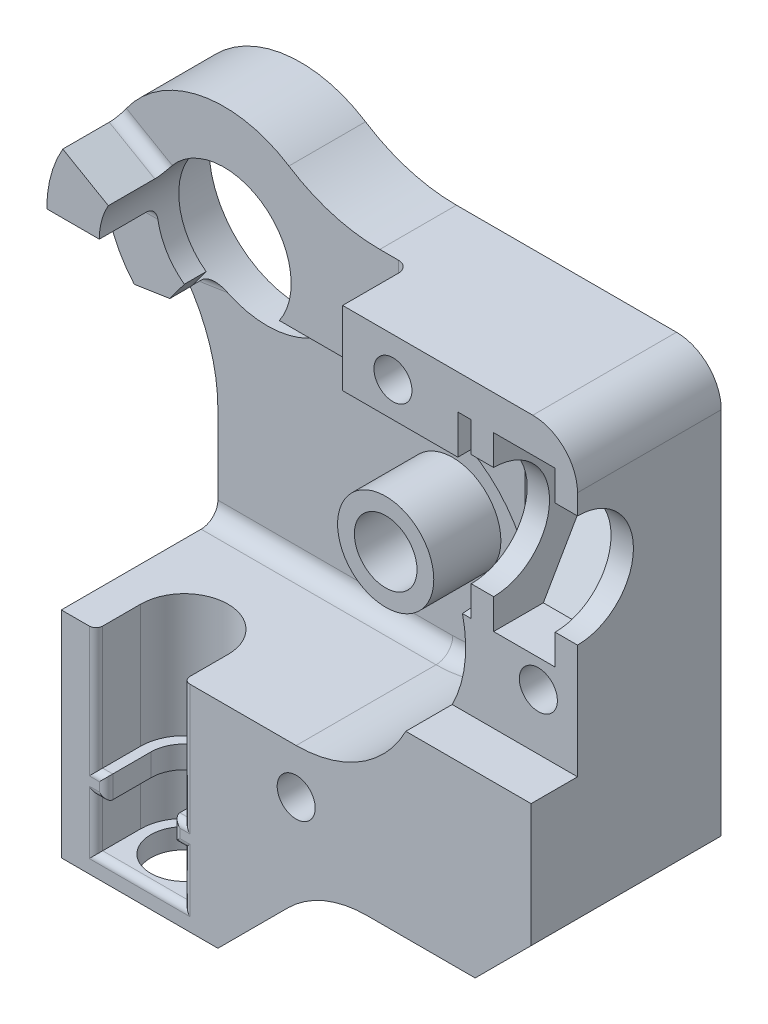
SolidWorks part; units mm, degrees
ref_plane "Plano frontal" through (0, 0, 0) normal (0, 0, 1) x (1, 0, 0)
ref_plane "Plano superior" through (0, 0, 0) normal (0, 1, 0) x (1, 0, 0)
ref_plane "Plano direito" through (0, 0, 0) normal (1, 0, 0) x (0, 0, -1)
sketch "Esboço1" plane through (0, 0, 0) normal (0, 0, 1) x (1, 0, 0)
  line L10 (16.6, -14.4) -> (0, 0) construction
  line L11 (-4.4, -16.8562) -> (-4.4, -44.6)
  line L12 (-4.4, -44.6) -> (9.6, -44.6)
  line L13 (9.6, -44.6) -> (15.8711, -38.3289)
  line L14 (22.9421, -35.4) -> (32.6, -35.4)
  line L15 (37.6, -30.4) -> (37.6, 2.6)
  line L16 (33.6, 6.6) -> (13.9259, 6.6)
  line L17 (32.6, -35.4) -> (37.6, -30.4)
  line L18 (16.6, -14.4) -> (34.1, -14.4) construction
  line L19 (16.6, -14.4) -> (16.6, -29.4) construction
  line L20 (37.6, -4.2) -> (-20.5781, -4.2) construction
  arc A10 (5.7979, 8.993) -> (-8.077, -7.0179) centre (0, 0) ccw
  circle A11 centre (0, 0) radius 8.2 construction
  arc A12 (37.6, 2.6) -> (33.6, 6.6) centre (33.6, 2.6) ccw
  arc A13 (-4.4, -16.8562) -> (-8.077, -7.0179) centre (-19.4, -16.8562) ccw
  arc A14 (13.9259, 6.6) -> (5.7979, 8.993) centre (13.9259, 21.6) cw
  arc A15 (15.8711, -38.3289) -> (22.9421, -35.4) centre (22.9421, -45.4) cw
  circle A16 centre (16.6, -14.4) radius 2.8
  circle A17 centre (34.1, -14.4) radius 1.7
  circle A18 centre (16.6, -29.4) radius 1.7
  circle A19 centre (0, 0) radius 4 construction
  circle A20 centre (21.1, 3.1) radius 1.7
  circle A21 centre (0, 0) radius 6
  point P41 (37.6, -35.4)
  dimension "D2" = 16.4
  dimension "D3" = 2.5
  dimension "D4" = 4.4
  dimension "D11" = 4
  dimension "D12" = 15
  dimension "D13" = 10
  dimension "D14" = 5.6
  dimension "D19" = 3.4
  dimension "D21" = 10.8
  dimension "D22" = 8
  dimension "D23" = 3.1
  dimension "D25" = 12
  dimension "D5" = 44.6
  dimension "D6" = 14
  dimension "D7" = 135
  dimension "D8" = 9.2
  dimension "D9" = 42
  dimension "D10" = 6.6
  dimension "D15" = 16.6
  dimension "D16" = 14.4
  dimension "D18" = 17.5
  dimension "D20" = 15
  dimension "D24" = 21.1
extrude "Ressalto-extrusão1" add sketch "Esboço1" along normal blind 17 contours L13 A15 L14 L17 L15 A12 L16 A14 A10 A13 L11 L12 A20 A18 A17 A16 region at (-4.6615, -11.3476, 0)
sketch "Esboço2" plane through (0, 0, 0) normal (0, 0, -1) x (-1, 0, 0)
  line L1 (-19.4257, 0.2) -> (-17.7514, 3.1)
  line L2 (-17.7514, 3.1) -> (-19.4257, 6)
  line L3 (-19.4257, 6) -> (-22.7743, 6)
  line L4 (-22.7743, 6) -> (-24.4486, 3.1)
  line L5 (-24.4486, 3.1) -> (-22.7743, 0.2)
  line L6 (-22.7743, 0.2) -> (-19.4257, 0.2)
  circle A0 centre (-21.1, 3.1) radius 2.9 construction
  dimension "D1" = 5.8
extrude "Corte-extrusão1" cut sketch "Esboço2" against normal blind 3.5
sketch "Esboço3" plane through (0, 0, 0) normal (0, 0, -1) x (-1, 0, 0)
  circle A0 centre (0, 0) radius 8.2
  dimension "D1" = 16.4
extrude "Corte-extrusão2" cut sketch "Esboço3" against normal blind 4.9
sketch "Esboço5" plane through (-4.4, 0, 0) normal (-1, 0, 0) x (0, 0, 1)
  line L5 (0, -44.6) -> (7, -44.6)
  line L6 (17, -44.6) -> (0, -44.6) construction
  line L7 (7, -44.6) -> (0, -37.6)
  line L8 (0, -16.8562) -> (0, -44.6) construction
  line L9 (0, -37.6) -> (0, -44.6)
  dimension "D1" = 7
  dimension "D2" = 7
extrude "Corte-extrusão3" cut sketch "Esboço5" against normal through all
sketch "Esboço6" plane through (0, -44.6, 0) normal (0, -1, 0) x (1, 0, 0)
  line L0 (-4.4, 17) -> (-4.4, 0) construction
  line L1 (-4.4, 17) -> (9.6, 17) construction
  circle A0 centre (2.6, 13) radius 3
  dimension "D1" = 7
  dimension "D3" = 6
  dimension "D2" = 4
sketch "Esboço7" plane through (0, 0, 17) normal (0, 0, 1) x (1, 0, 0)
  line L5 (16.6, -3.4) -> (7.7904, -3.4)
  line L6 (16.6, -25.4) -> (-4.4, -25.4)
  line L7 (-4.4, -16.8562) -> (-4.4, -44.6) construction
  line L8 (-5.0333, -6.8495) -> (-6.6181, -9.0061)
  line L9 (-4.4, -25.4) -> (-4.4, -16.8562)
  line L10 (7.7904, -3.4) -> (4.9437, -3.4)
  line L11 (-5.0333, -6.8495) -> (-3.5529, -4.8349)
  arc A3 (16.6, -25.4) -> (16.6, -3.4) centre (16.6, -14.4) ccw
  arc A5 (-5.0333, -6.8495) -> (7.7904, -3.4) centre (0, 0) ccw
  arc A6 (-4.4, -16.8562) -> (-8.077, -7.0179) centre (-19.4, -16.8562) ccw construction
  arc A7 (-4.4, -16.8562) -> (-6.6181, -9.0061) centre (-19.4, -16.8562) ccw
  circle A8 centre (0, 0) radius 6 construction
  arc A9 (-3.5529, -4.8349) -> (4.9437, -3.4) centre (0, 0) ccw
  circle M16 centre (0, 0) radius 6
  circle M20 centre (16.6, -14.4) radius 2.8
  arc M30 (-8.077, -7.0179) -> (-4.4, -16.8562) centre (-19.4, -16.8562) cw
  line M31 (-4.4, -16.8562) -> (-4.4, -44.6)
  dimension "D1" = 22
  dimension "D2" = 17
  dimension "D3" = 126.31
extrude "Corte-extrusão4" cut sketch "Esboço7" against normal blind 14 contours L11 A5 L10 M16 | A5 L8 L6 A3 L5 M30 M31 M20 region at (10.8464, -15.0745, 17) region at (1.4573, -6.3002, 17)
sketch "Esboço8" plane through (0, 0, 17) normal (0, 0, 1) x (1, 0, 0)
  line L0 (26.398, -19.4) -> (37.6, -19.4)
  line L1 (37.6, -30.4) -> (37.6, 2.6) construction
  line L2 (33.6, 6.6) -> (13.9259, 6.6) construction
  line L13 (-6.6181, -9.0061) -> (-3.5529, -4.8349)
  line L14 (4.9437, -3.4) -> (16.6, -3.4)
  line L15 (16.6, -25.4) -> (-4.4, -25.4)
  line L16 (-4.4, -25.4) -> (-4.4, -44.6)
  line L17 (-4.4, -44.6) -> (9.6, -44.6)
  line L18 (9.6, -44.6) -> (15.8711, -38.3289)
  line L19 (22.9421, -35.4) -> (32.6, -35.4)
  line L20 (32.6, -35.4) -> (37.6, -30.4)
  line L21 (37.6, -30.4) -> (37.6, 2.6)
  line L22 (33.6, 6.6) -> (13.9259, 6.6)
  line L23 (-6.6181, -9.0061) -> (-3.5529, -4.8349)
  line L24 (4.9437, -3.4) -> (16.6, -3.4)
  line L31 (37.6, -19.4) -> (37.6, 2.6)
  line L32 (33.6, 6.6) -> (13.9259, 6.6)
  arc A0 (16.6, -25.4) -> (16.6, -3.4) centre (16.6, -14.4) ccw construction
  arc A8 (-6.6181, -9.0061) -> (-8.077, -7.0179) centre (-19.4, -16.8562) ccw
  arc A9 (4.9437, -3.4) -> (-3.5529, -4.8349) centre (0, 0) ccw
  arc A10 (16.6, -25.4) -> (16.6, -3.4) centre (16.6, -14.4) ccw
  arc A11 (22.9421, -35.4) -> (15.8711, -38.3289) centre (22.9421, -45.4) ccw
  arc A12 (37.6, 2.6) -> (33.6, 6.6) centre (33.6, 2.6) ccw
  arc A13 (5.7979, 8.993) -> (13.9259, 6.6) centre (13.9259, 21.6) ccw
  arc A14 (5.7979, 8.993) -> (-8.077, -7.0179) centre (0, 0) ccw
  arc A15 (-6.6181, -9.0061) -> (-8.077, -7.0179) centre (-19.4, -16.8562) ccw
  arc A16 (4.9437, -3.4) -> (-3.5529, -4.8349) centre (0, 0) ccw
  arc A17 (26.398, -19.4) -> (16.6, -3.4) centre (16.6, -14.4) ccw
  arc A19 (37.6, 2.6) -> (33.6, 6.6) centre (33.6, 2.6) ccw
  arc A20 (5.7979, 8.993) -> (13.9259, 6.6) centre (13.9259, 21.6) ccw
  arc A21 (5.7979, 8.993) -> (-8.077, -7.0179) centre (0, 0) ccw
  dimension "D1" = 26
  dimension "D2" = 0
extrude "Corte-extrusão5" cut sketch "Esboço8" against normal blind 5
sketch "Esboço9" plane through (0, 0, 3) normal (0, 0, 1) x (1, 0, 0)
  circle A0 centre (16.6, -14.4) radius 4.3
  circle A1 centre (16.6, -14.4) radius 2.8 construction
  circle A2 centre (16.6, -14.4) radius 2.8
  dimension "D1" = 8.6
extrude "Ressalto-extrusão2" add sketch "Esboço9" along normal blind 6
extrude "Corte-extrusão6" cut sketch "Esboço6" against normal up to surface (19.2 mm away) up to face at (6.1, -25.4, 10)
ref_plane "Plano1" through (0, -42.8, 0) normal (0, -1, 0) x (-1, 0, 0)
sketch "Esboço10" plane through (0, -42.8, 0) normal (0, -1, 0) x (-1, 0, 0)
  line L0 (-6.5, -13) -> (-6.5, -21)
  line L1 (-6.5, -21) -> (1.3, -21)
  line L2 (1.3, -21) -> (1.3, -13)
  arc A0 (1.3, -13) -> (-6.5, -13) centre (-2.6, -13) ccw
  dimension "D1" = 7.8
  dimension "D2" = 8
extrude "Corte-extrusão7" cut sketch "Esboço10" against normal blind 4.4
ref_plane "Plano2" through (0, -36.4, 0) normal (0, -1, 0) x (-1, 0, 0)
sketch "Esboço11" plane through (0, -36.4, 0) normal (0, -1, 0) x (-1, 0, 0)
  line L0 (-6.5, -13) -> (-6.5, -19.7153)
  line L1 (-6.5, -19.7153) -> (1.3, -19.7153)
  line L2 (1.3, -19.7153) -> (1.3, -13)
  arc A0 (1.3, -13) -> (-6.5, -13) centre (-2.6, -13) ccw
  dimension "D1" = 7.8
extrude "Corte-extrusão8" cut sketch "Esboço11" against normal up to surface (11 mm away) up to face at (2.6, -25.4, 16)
sketch "Esboço12" plane through (0, -38.4, 0) normal (0, -1, 0) x (1, 0, 0)
  line L0 (-0.4, 13) -> (-0.4, 18.9694)
  line L1 (-0.4, 18.9694) -> (5.6, 18.9694)
  line L2 (5.6, 18.9694) -> (5.6, 13)
  arc A0 (-0.4, 13) -> (5.6, 13) centre (2.6, 13) ccw
  dimension "D1" = 6
extrude "Corte-extrusão9" cut sketch "Esboço12" against normal up to surface (2 mm away) up to face at (2.6, -36.4, 14.025)
fillet "Filete2" radius 0.6 11 edges at (2.6, -42.8, 17) (6.5, -40.6, 17) (6.05, -38.4, 17) (5.6, -37.4, 17) (6.05, -36.4, 17) (6.5, -30.9, 17) (-1.3, -30.9, 17) (-0.85, -36.4, 17) (-0.4, -37.4, 17) (-0.85, -38.4, 17) (-1.3, -40.6, 17)
sketch "Esboço13" plane through (0, 0, 12) normal (0, 0, 1) x (1, 0, 0)
  line L0 (16.6, 6.6) -> (16.6, -3.4)
  line L1 (33.6, 6.6) -> (13.9259, 6.6) construction
  line L2 (37.6, -19.4) -> (37.6, 2.6) construction
  line L3 (-6, 0) -> (-10.7, 0)
  line L4 (-5.1962, 3) -> (-9.2665, 5.35)
  line L5 (0, 0) -> (-5.1962, 3) construction
  line L8 (26.398, -19.4) -> (37.6, -19.4)
  line L9 (37.6, -19.4) -> (37.6, 2.6)
  line L10 (33.6, 6.6) -> (13.9259, 6.6)
  line L11 (-6.6181, -9.0061) -> (-3.5529, -4.8349)
  line L12 (4.9437, -3.4) -> (16.6, -3.4)
  line L15 (16.6, 6.6) -> (13.9259, 6.6)
  line L16 (-6.6181, -9.0061) -> (-3.5529, -4.8349)
  line L17 (4.9437, -3.4) -> (16.6, -3.4)
  arc A0 (26.398, -19.4) -> (16.6, -3.4) centre (16.6, -14.4) ccw construction
  arc A7 (26.398, -19.4) -> (16.6, -3.4) centre (16.6, -14.4) ccw
  arc A8 (37.6, 2.6) -> (33.6, 6.6) centre (33.6, 2.6) ccw
  arc A9 (5.7979, 8.993) -> (13.9259, 6.6) centre (13.9259, 21.6) ccw
  arc A10 (5.7979, 8.993) -> (-8.077, -7.0179) centre (0, 0) ccw
  arc A11 (-6.6181, -9.0061) -> (-8.077, -7.0179) centre (-19.4, -16.8562) ccw
  arc A12 (4.9437, -3.4) -> (-3.5529, -4.8349) centre (0, 0) ccw
  arc A15 (5.7979, 8.993) -> (13.9259, 6.6) centre (13.9259, 21.6) ccw
  arc A16 (5.7979, 8.993) -> (-8.077, -7.0179) centre (0, 0) ccw
  arc A17 (-6.6181, -9.0061) -> (-8.077, -7.0179) centre (-19.4, -16.8562) ccw
  arc A18 (4.9437, -3.4) -> (-3.5529, -4.8349) centre (0, 0) ccw
  line M19 (33.6, 6.6) -> (13.9259, 6.6)
  arc M20 (13.9259, 6.6) -> (5.7979, 8.993) centre (13.9259, 21.6) cw
  arc M21 (5.7979, 8.993) -> (-8.077, -7.0179) centre (0, 0) ccw
  arc M22 (-8.077, -7.0179) -> (-6.6181, -9.0061) centre (-19.4, -16.8562) cw
  line M23 (-6.6181, -9.0061) -> (-3.5529, -4.8349)
  arc M24 (-3.5529, -4.8349) -> (4.9437, -3.4) centre (0, 0) cw
  line M25 (4.9437, -3.4) -> (16.6, -3.4)
  dimension "D1" = 21
  dimension "D3" = 30
  dimension "D2" = 0
extrude "Corte-extrusão10" cut sketch "Esboço13" against normal offset from surface (5.15 mm away) 1.95 contours L0 M19 M20 M21 M22 M23 M24 M25 | L3 M24 M21 M22 M23 region at (6.3661, 3.9454, 12) region at (-7.3652, -3.7768, 12) up to face at (-0.2668, 1.1825, 4.9)
sketch "Esboço18" plane through (0, 0, 12) normal (0, 0, 1) x (1, 0, 0)
  line L4 (33.6, 6.6) -> (16.6, 6.6)
  line L5 (16.6, 6.6) -> (16.6, -3.4)
  line L6 (26.398, -19.4) -> (37.6, -19.4)
  line L7 (37.6, -19.4) -> (37.6, 2.6)
  line L8 (33.6, 6.6) -> (16.6, 6.6)
  line L9 (16.6, 6.6) -> (16.6, -3.4)
  line L10 (26.398, -19.4) -> (37.6, -19.4)
  line L11 (37.6, -19.4) -> (37.6, 2.6)
  circle A0 centre (21.1, 3.1) radius 1.7 construction
  circle A1 centre (21.1, 3.1) radius 1.7
  arc A2 (26.398, -19.4) -> (16.6, -3.4) centre (16.6, -14.4) ccw
  arc A3 (37.6, 2.6) -> (33.6, 6.6) centre (33.6, 2.6) ccw
  arc A4 (26.398, -19.4) -> (16.6, -3.4) centre (16.6, -14.4) ccw
  arc A5 (37.6, 2.6) -> (33.6, 6.6) centre (33.6, 2.6) ccw
  circle A6 centre (34.1, -14.4) radius 1.7 construction
  circle A7 centre (34.1, -14.4) radius 1.7
  dimension "D1" = 0
extrude "Ressalto-extrusão3" add sketch "Esboço18" along normal blind 0.85
fillet "Filete3" radius 1 2 edges at (-8.35, 0, 6.85) (-7.2313, 4.175, 6.85)
sketch "Esboço14" plane through (37.6, 0, 0) normal (1, 0, 0) x (0, 0, -1)
  line L0 (0, -30.4) -> (0, 2.6) construction
  line L1 (-6.85, 6.6) -> (0, 6.6) construction
  circle A0 centre (-12.85, -4.2) radius 5
  dimension "D1" = 12.85
  dimension "D3" = 10
  dimension "D2" = 10.8
extrude "Corte-extrusão11" cut sketch "Esboço14" against normal blind 10.7
ref_plane "Plano3" through (35.6, 0, 0) normal (1, 0, 0) x (0, 0, -1)
sketch "Esboço16" plane through (35.6, 0, 0) normal (1, 0, 0) x (0, 0, -1)
  line L0 (-12.85, -9.2) -> (-12.85, 0.8) construction
  line L1 (-3.9588, -4.2) -> (-8.4044, 3.5)
  line L2 (-8.4044, 3.5) -> (-17.2956, 3.5)
  line L3 (-17.2956, 3.5) -> (-21.7412, -4.2)
  line L4 (-21.7412, -4.2) -> (-17.2956, -11.9)
  line L5 (-17.2956, -11.9) -> (-8.4044, -11.9)
  line L6 (-8.4044, -11.9) -> (-3.9588, -4.2)
  circle A2 centre (-12.85, -4.2) radius 7.7 construction
  dimension "D1" = 15.4
extrude "Corte-extrusão13" cut sketch "Esboço16" against normal blind 5.5
sketch "Esboço17" plane through (0, 0, 12.85) normal (0, 0, 1) x (1, 0, 0)
  line L0 (16.6, 0) -> (26.9, 0)
  line L1 (16.6, 6.6) -> (16.6, -3.4) construction
  line L3 (33.6, 6.6) -> (16.6, 6.6) construction
  line L16 (26.9, -9.2) -> (26.9, 0.8)
  line L17 (35.6, -11.9) -> (30.1, -11.9)
  line L18 (35.6, 3.5) -> (35.6, 0.8)
  line L19 (35.6, 0.8) -> (37.6, 0.8)
  line L29 (30.1, -11.9) -> (30.1, -9.2)
  line L30 (33.6, 6.6) -> (16.6, 6.6)
  line L31 (16.6, 6.6) -> (16.6, -3.4)
  line L32 (26.9, -9.2) -> (26.9, 0)
  line L39 (16.6, 0) -> (16.6, -3.4)
  line L47 (30.1, -9.2) -> (26.9, -9.2)
  line L48 (26.9, -9.2) -> (26.2933, -9.2)
  line L49 (26.9, 0.8) -> (30.1, 0.8)
  line L51 (30.1, 0.8) -> (30.1, 3.5)
  line L53 (30.1, 3.5) -> (35.6, 3.5)
  line L55 (37.6, 0.8) -> (37.6, 2.6)
  line L57 (26.398, -19.4) -> (37.6, -19.4)
  line L59 (37.6, -19.4) -> (37.6, -9.2)
  line L61 (37.6, -9.2) -> (35.6, -9.2)
  line L63 (35.6, -9.2) -> (35.6, -11.9)
  arc A7 (26.398, -19.4) -> (16.6, -3.4) centre (16.6, -14.4) ccw
  arc A8 (37.6, 2.6) -> (33.6, 6.6) centre (33.6, 2.6) ccw
  arc A9 (26.2933, -9.2) -> (16.6, -3.4) centre (16.6, -14.4) ccw
  dimension "D1" = 6.6
  dimension "D3" = 0
extrude "Corte-extrusão14" cut sketch "Esboço17" against normal blind 6.85
sketch "Esboço19" plane through (0, 0, 6) normal (0, 0, 1) x (1, 0, 0)
  line L4 (16.6, 0) -> (16.6, -3.4)
  line L5 (26.9, -9.2) -> (26.9, 0)
  line L7 (26.9, 0) -> (16.6, 0)
  line L8 (16.6, 0) -> (16.6, -3.4)
  line L9 (26.9, -9.2) -> (26.9, 0)
  line L11 (26.9, 0) -> (16.6, 0)
  line L29 (26.2933, -9.2) -> (26.9, -9.2)
  line L30 (26.2933, -9.2) -> (26.9, -9.2)
  arc A1 (26.2933, -9.2) -> (16.6, -3.4) centre (16.6, -14.4) ccw
  arc A2 (26.2933, -9.2) -> (16.6, -3.4) centre (16.6, -14.4) ccw
  line M6 (16.6, 0) -> (16.6, -3.4)
  arc M7 (16.6, -3.4) -> (26.2933, -9.2) centre (16.6, -14.4) cw
  line M8 (26.9, -9.2) -> (26.9, 0)
  line M10 (26.9, 0) -> (16.6, 0)
  dimension "D1" = 0
extrude "Ressalto-extrusão4" add sketch "Esboço19" along normal up to surface (0.85 mm away) contours M10 M6 M7 M8 region at (22.7316, -2.9769, 6) up to face at (7.9799, 4.0392, 6.85)
chamfer "Chanfro3" distance 3 angle 45 1 edges at (-6.6181, -9.0061, 4.925) first distance on face at (-5.0089, -6.8163, 4.9167)
fillet "Filete4" radius 1 2 edges at (16.6, 3.3, 6.85) (-6.451, -6.8346, 3)
fillet "Filete5" radius 1.5 3 edges at (12.031, -3.4, 3) (27.6, -14.4, 3) (6.1, -25.4, 3)
ref_plane "Plano4" through (28.1, 0, 0) normal (1, 0, 0) x (0, 0, -1)
sketch "Esboço20" plane through (28.1, 0, 0) normal (1, 0, 0) x (0, 0, -1)
  circle A0 centre (-12.85, -4.2) radius 7.7
  dimension "D1" = 15.4
extrude "Corte-extrusão15" cut sketch "Esboço20" against normal up to surface (1.2 mm away) up to face at (26.9, 0.3319, 11.9264)
sketch "Esboço21" plane through (0, 0, 12.85) normal (0, 0, 1) x (1, 0, 0)
  line L2 (26.9, -10.5387) -> (26.9, -9.2)
  line L3 (26.9, -9.2) -> (26.2933, -9.2)
  line L4 (26.9, -10.5387) -> (26.9, -9.2)
  line L5 (26.9, -9.2) -> (26.2933, -9.2)
  arc A1 (26.9, -10.5387) -> (26.2933, -9.2) centre (16.6, -14.4) ccw
  arc A2 (26.9, -10.5387) -> (26.2933, -9.2) centre (16.6, -14.4) ccw
  dimension "D1" = 0
extrude "Corte-extrusão16" cut sketch "Esboço21" against normal up to surface (6 mm away) up to face at (14.1362, 0.5189, 6.85)
